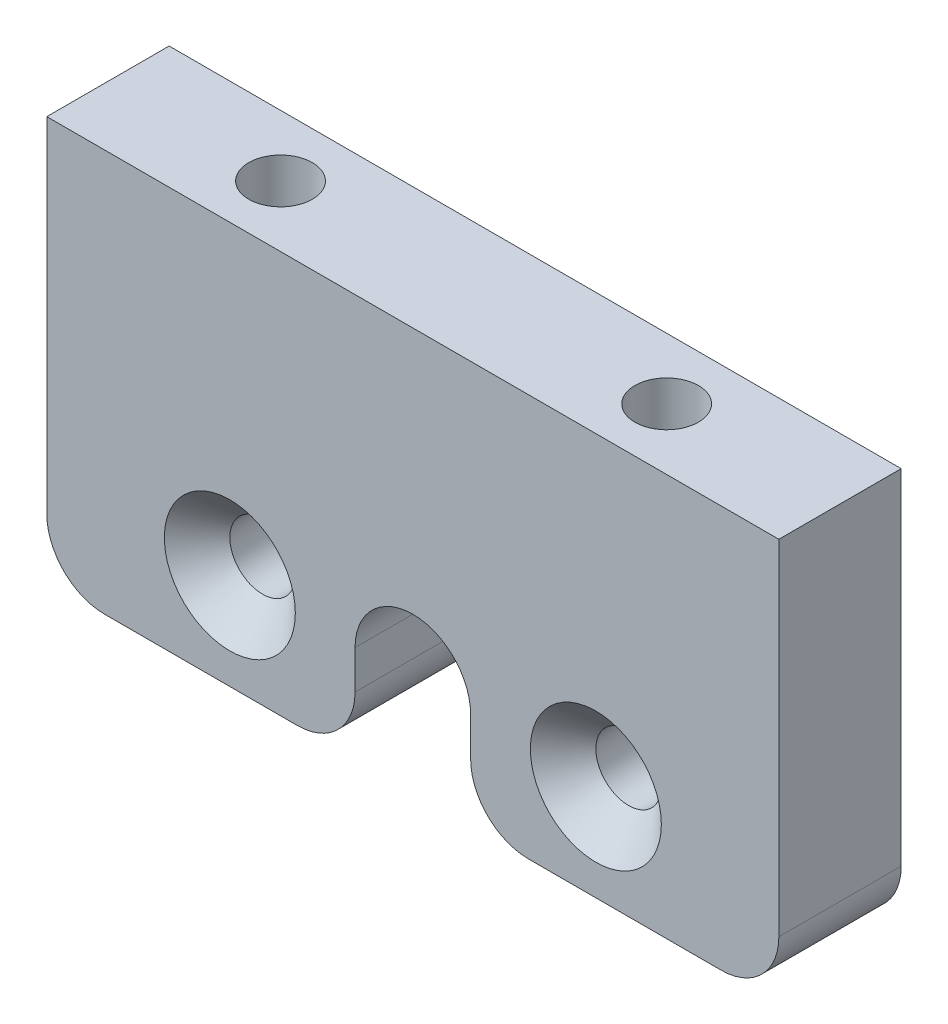
SolidWorks part; units mm, degrees
ref_plane "Front Plane" through (0, 0, 0) normal (0, 0, 1) x (1, 0, 0)
ref_plane "Top Plane" through (0, 0, 0) normal (0, 1, 0) x (1, 0, 0)
ref_plane "Right Plane" through (0, 0, 0) normal (1, 0, 0) x (0, 0, -1)
sketch "Sketch1" plane through (0, 0, -22.6443) normal (0, 0, 1) x (1, 0, 0)
  line L0 (-5.0687, 6.9987) -> (0.5439, 6.9987) construction
  line L1 (3, 6.9987) -> (3, 1.9987)
  line L2 (-3, 6.9987) -> (-3, 1.9987)
  line L3 (3, 1.9987) -> (19, 1.9987)
  line L4 (-3, 1.9987) -> (-19, 1.9987)
  line L5 (19, 1.9987) -> (19, 22.8687)
  line L6 (19, 22.8687) -> (-19, 22.8687)
  line L7 (-19, 22.8687) -> (-19, 1.9987)
  circle A0 centre (0, 6.9987) radius 9.5 construction
  circle A1 centre (9.5, 6.9987) radius 1.7
  circle A2 centre (-9.5, 6.9987) radius 1.7
  arc A4 (3, 6.9987) -> (-3, 6.9987) centre (0, 6.9987) ccw
extrude "Boss-Extrude1" add sketch "Sketch1" along normal blind 6.35
chamfer "Chamfer1" distance 1.7 angle 45 2 edges at (-7.8, 6.9987, -16.2943) (11.2, 6.9987, -16.2943)
sketch "Sketch2" plane through (0, 22.8687, 0) normal (0, 1, 0) x (1, 0, 0)
  line L0 (19, 19.4693) -> (13.1436, 19.4693) construction
  line L1 (19, 16.2943) -> (19, 22.6443) construction
  line L2 (0, 26.9037) -> (0, 22.3463) construction
  line L4 (-10, 26.9037) -> (-10, 22.3463) construction
  line L5 (10, 26.9037) -> (10, 22.3463) construction
  circle A0 centre (10, 19.4693) radius 1.65
  circle A1 centre (-10.0429, 19.4693) radius 1.65
  point P15 (19, 19.4693)
  dimension "D3" = 3.3
  dimension "D4" = 3.3
  dimension "D1" = 10
  dimension "D2" = 10
extrude "Cut-Extrude1" cut sketch "Sketch2" against normal blind 10
fillet "Fillet1" radius 3 4 edges at (-19, 1.9987, -19.4693) (-3, 1.9987, -19.4693) (3, 1.9987, -19.4693) (19, 1.9987, -19.4693)
